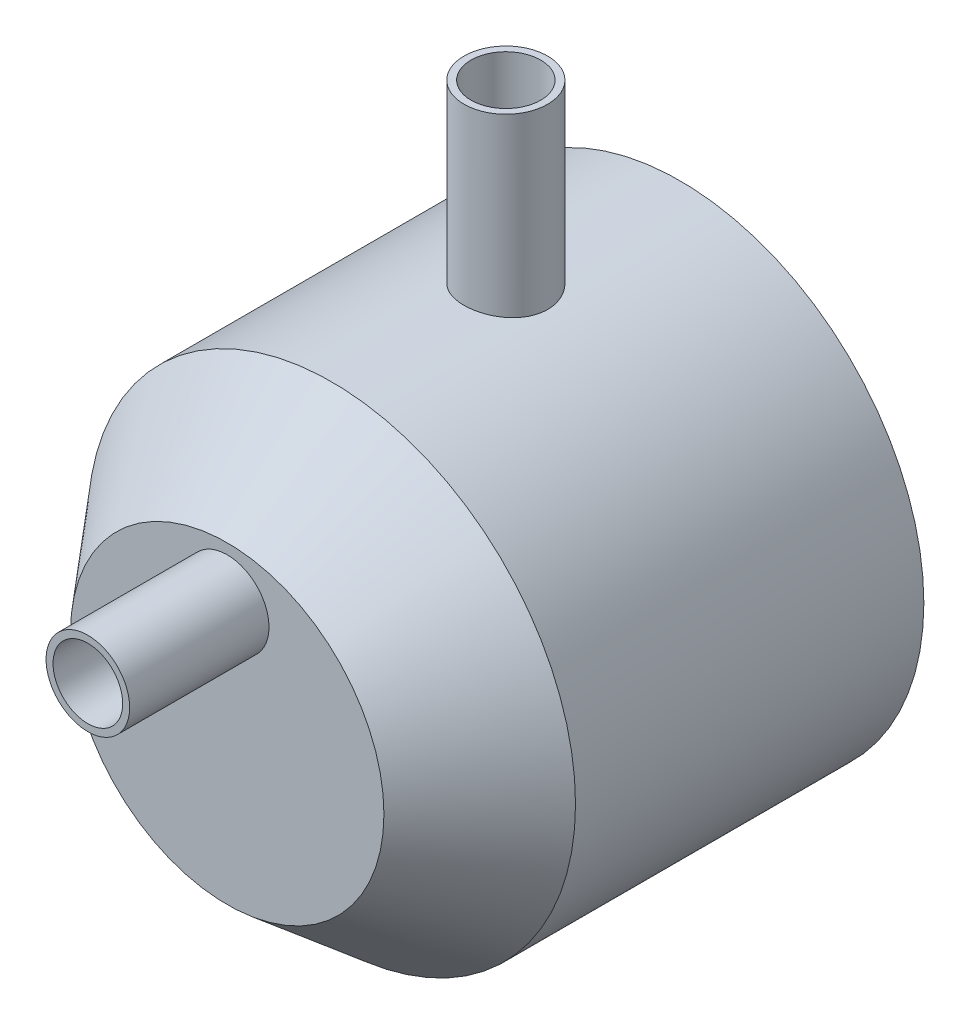
SolidWorks part; units mm, degrees
ref_plane "前视基准面" through (0, 0, 0) normal (0, 0, 1) x (1, 0, 0)
ref_plane "上视基准面" through (0, 0, 0) normal (0, 1, 0) x (1, 0, 0)
ref_plane "右视基准面" through (0, 0, 0) normal (1, 0, 0) x (0, 0, -1)
sketch "草图1" plane through (0, 0, 0) normal (0, 0, 1) x (1, 0, 0)
  circle A0 centre (0, 0) radius 25
  circle A1 centre (0, 0) radius 35
  dimension "D1" = 50
  dimension "D2" = 70
extrude "凸台-拉伸1" add sketch "草图1" along normal mid plane 50
sketch "草图2" plane through (0, 0, -25) normal (0, 0, -1) x (-1, 0, 0)
  circle A0 centre (0, 0) radius 28.75 construction
  circle A1 centre (0, 28.75) radius 1.5
  circle A2 centre (0, 0) radius 28.75 construction
  circle A3 centre (28.75, 0) radius 1.5
  circle A4 centre (0, 0) radius 28.75 construction
  circle A5 centre (0, -28.75) radius 1.5
  circle A6 centre (0, 0) radius 28.75 construction
  circle A7 centre (-28.75, 0) radius 1.5
  dimension "D1" = 57.5
  dimension "D2" = 3
  dimension "D3" = 4
extrude "切除-拉伸1" cut sketch "草图2" against normal blind 10
sketch "草图3" plane through (0, 0, 25) normal (0, 0, 1) x (1, 0, 0)
  circle A0 centre (0, 0) radius 35
ref_plane "基准面1" through (0, 0, 40) normal (0, 0, 1) x (1, 0, 0)
sketch "草图4" plane through (0, 0, 40) normal (0, 0, 1) x (1, 0, 0)
  circle A0 centre (0, 0) radius 22.5
  dimension "D1" = 45
loft "放样1" add profiles "草图4", "草图3" connector at (-20.6213, 9.0007, 40) connector at (-31.1352, 15.9876, 25)
sketch "草图5" plane through (0, 0, 25) normal (0, 0, -1) x (-1, 0, 0)
  circle A0 centre (0, 0) radius 25
ref_plane "基准面2" through (0, 0, 37) normal (0, 0, 1) x (1, 0, 0)
sketch "草图6" plane through (0, 0, 37) normal (0, 0, 1) x (1, 0, 0)
  circle A0 centre (0, 0) radius 19
  dimension "D1" = 38
loft "切除-放样1" cut profiles "草图6", "草图5" connector at (-17.4135, 7.6006, 37) connector at (-12.9148, 21.4058, 25)
ref_plane "基准面3" through (0, 60, 0) normal (0, 1, 0) x (1, 0, 0)
sketch "草图7" plane through (0, 60, 0) normal (0, 1, 0) x (1, 0, 0)
  circle A0 centre (0, 0) radius 5
  circle A1 centre (0, 0) radius 6
  dimension "D1" = 10
  dimension "D2" = 12
extrude "凸台-拉伸2" add sketch "草图7" against normal up to surface (25 mm away) up to face at (35, 0, 25)
sketch "草图8" plane through (0, 60, 0) normal (0, 1, 0) x (1, 0, 0)
  circle A0 centre (0, 0) radius 10
ref_plane "基准面4" through (0, 0, 60) normal (0, 0, 1) x (1, 0, 0)
sketch "草图9" plane through (0, 0, 60) normal (0, 0, 1) x (1, 0, 0)
  circle A0 centre (0, 15) radius 6
  circle A1 centre (0, 15) radius 5
  point P3 (0, 15)
  dimension "D1" = 12
  dimension "D2" = 10
  dimension "D3" = 15
extrude "凸台-拉伸3" add sketch "草图9" against normal up to surface (20 mm away) up to face at (22.5, 0, 40)
